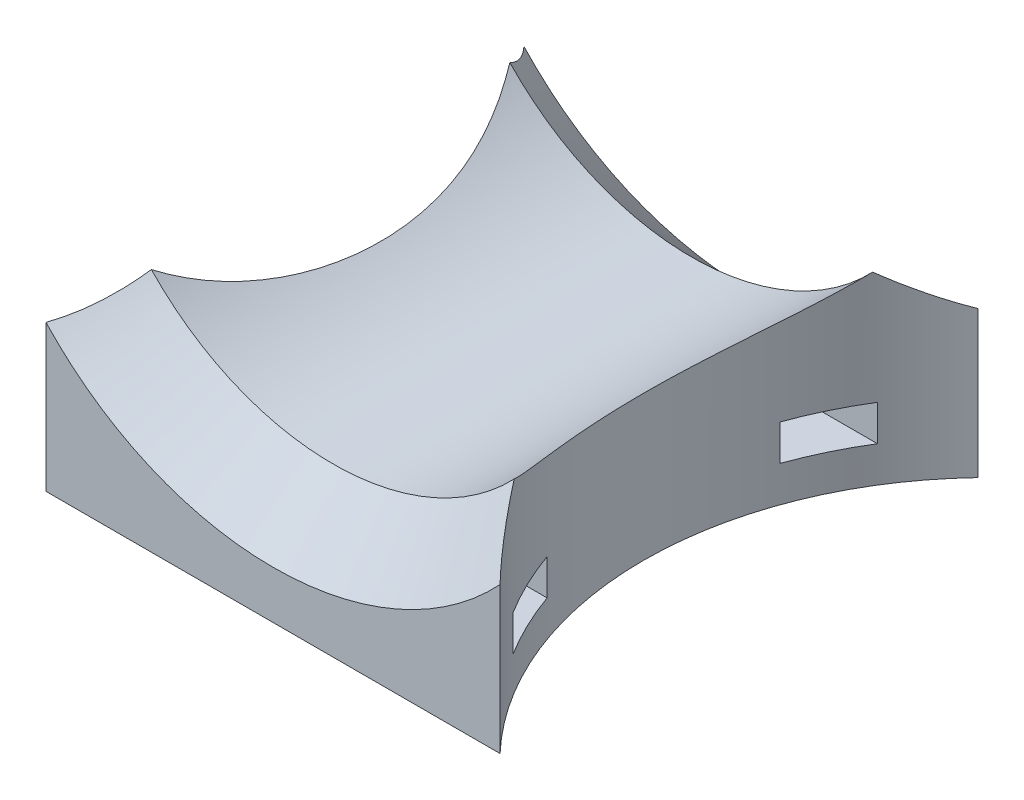
SolidWorks part; units mm, degrees
material "ABS"
ref_plane "Front Plane" through (0, 0, 0) normal (0, 0, 1) x (1, 0, 0)
ref_plane "Top Plane" through (0, 0, 0) normal (0, 1, 0) x (1, 0, 0)
ref_plane "Right Plane" through (0, 0, 0) normal (1, 0, 0) x (0, 0, -1)
sketch "Sketch1" plane through (0, 0, 0) normal (0, 0, 1) x (1, 0, 0)
  line L0 (0, 36.8586) -> (0, -36.8586) construction
  line L1 (-15, 36.8586) -> (-15, -36.8586) construction
  line L2 (15, 36.8586) -> (15, -36.8586) construction
  circle A0 centre (0, 0) radius 20 construction
  circle A1 centre (0, 0) radius 21 construction
  dimension "D2" = 40
  dimension "D3" = 42
  dimension "D1" = 30
sketch "Sketch3" plane through (0, 0, 0) normal (0, 0, 1) x (1, 0, 0)
  line L1 (0, 36.8586) -> (0, -36.8586) construction
  line L2 (-27.5, -30) -> (27.5, -30)
  line L3 (-27.5, -30) -> (-27.5, 0)
  line L4 (-21, 0) -> (-27.5, 0)
  line L5 (27.5, -30) -> (27.5, 0)
  line L7 (21, 0) -> (-21, 0) construction
  line L8 (27.5, 0) -> (21, 0)
  arc A0 (-21, 0) -> (21, 0) centre (0, 0) ccw
  circle A2 centre (0, 0) radius 21 construction
  point P0 (0, 0)
  point P1 (0, 0)
  dimension "D1" = 55
  dimension "D3" = 30
sketch "Sketch4" plane through (0, 0, 0) normal (0, 1, 0) x (1, 0, 0)
  line L1 (0, 17.0682) -> (0, -18.3679) construction
  circle A0 centre (-40, 0) radius 29
  circle A1 centre (40, 0) radius 29
  point P2 (0, 0)
  dimension "D1" = 58
  dimension "D2" = 80
extrude "Boss-Extrude1" add sketch "Sketch3" along normal mid plane 40
extrude "Cut-Extrude1" cut sketch "Sketch4" against normal through all
chamfer "Chamfer1" distance 5 angle 45 2 edges at (0, -21, -20) (0, -21, 20)
sketch "Sketch5" plane through (0, 0, 0) normal (1, 0, 0) x (0, 0, -1)
  line L0 (0, -30) -> (0, -17.8885) construction
  line L1 (-20, -30) -> (20, -30) construction
  line L2 (15.25, -27) -> (9.75, -24) construction
  line L3 (-15.25, -24) -> (-9.75, -24)
  line L4 (-15.25, -24) -> (-15.25, -27)
  line L5 (-15.25, -27) -> (-9.75, -27)
  line L6 (-9.75, -24) -> (-9.75, -27)
  line L7 (-15.25, -24) -> (-9.75, -27) construction
  line L8 (-15.25, -27) -> (-9.75, -24) construction
  line L9 (15.25, -24) -> (9.75, -27) construction
  line L10 (9.75, -24) -> (9.75, -27)
  line L11 (15.25, -27) -> (9.75, -27)
  line L12 (15.25, -24) -> (15.25, -27)
  line L13 (15.25, -24) -> (9.75, -24)
  spline S0 degree 3 poles (-15, -14.5103) (-14.4901, -14.8327) (-13.958, -15.1262) (-12.8494, -15.6623) (-12.2701, -15.9058) (-10.4949, -16.5576) (-9.2595, -16.8912) (-7.3338, -17.2804) (-6.6768, -17.3917) (-5.355, -17.5782) (-4.6904, -17.6535) (-2.6862, -17.8323) (-1.3362, -17.8893) (0.7095, -17.8881) (1.3946, -17.8729) (2.7476, -17.8127) (3.4186, -17.7679) (5.4151, -17.5869) (6.7244, -17.4051) (8.6531, -17.013) (9.2903, -16.8617) (10.5241, -16.5192) (11.1243, -16.3274) (12.8741, -15.682) (13.9733, -15.1594) (15, -14.5103) knots 0 0 0 0 0.0625 0.0625 0.125 0.125 0.25 0.25 0.3125 0.3125 0.375 0.375 0.5 0.5 0.5625 0.5625 0.625 0.625 0.75 0.75 0.8125 0.8125 0.875 0.875 1 1 1 1 construction
  point P7 (-12.5, -25.5)
  point P16 (12.5, -25.5)
  dimension "D1" = 5.5
  dimension "D2" = 3
  dimension "D3" = 3
  dimension "D4" = 25
extrude "Cut-Extrude2" cut sketch "Sketch5" against normal blind 3 and the other way up to next
sketch "Sketch7" plane through (0, -30, 0) normal (0, -1, 0) x (1, 0, 0)
  line L0 (0, 20) -> (0, -20) construction
  line L1 (-19, 20) -> (19, 20) construction
  line L2 (-19, -20) -> (19, -20) construction
  line L3 (-11, 0) -> (11, 0) construction
  arc A0 (-19, -20) -> (-19, 20) centre (-40, 0) ccw construction
  arc A1 (19, 20) -> (19, -20) centre (40, 0) ccw construction
  circle A2 centre (0, 12.5) radius 1.8
  circle A3 centre (0, -12.5) radius 1.8
  dimension "D1" = 3.6
  dimension "D2" = 25
extrude "Cut-Extrude3" cut sketch "Sketch7" against normal blind 6
